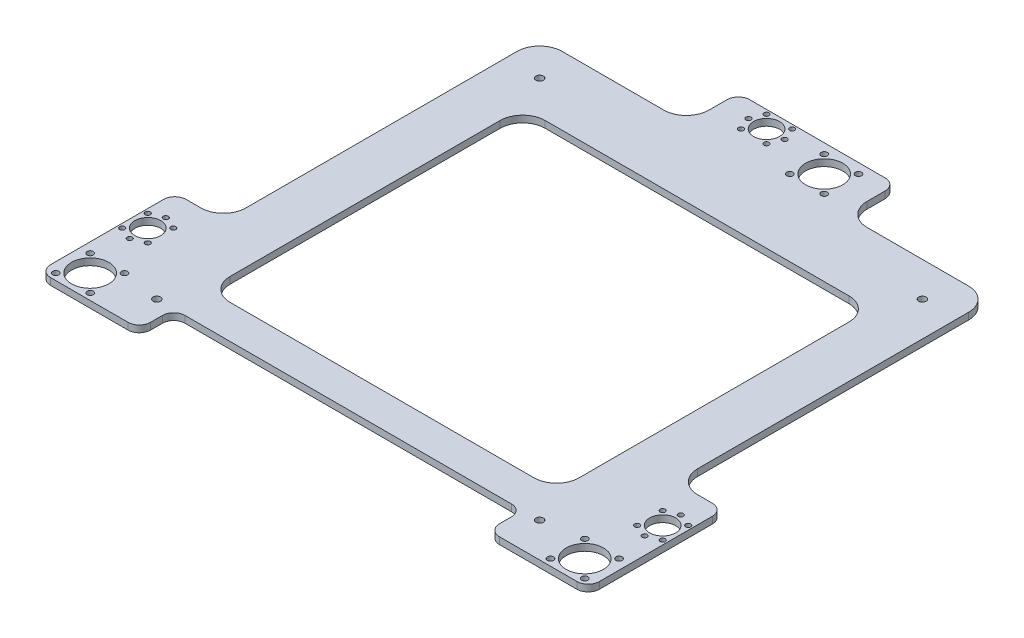
SolidWorks part; units mm, degrees
material "Plain Carbon Steel"
ref_plane "Front Plane" through (0, 0, 0) normal (0, 0, 1) x (1, 0, 0)
ref_plane "Top Plane" through (0, 0, 0) normal (0, 1, 0) x (1, 0, 0)
ref_plane "Right Plane" through (0, 0, 0) normal (1, 0, 0) x (0, 0, -1)
sketch "Sketch1" plane through (0, 0, 0) normal (0, 1, 0) x (1, 0, 0)
  line L0 (-243, -200) -> (243, -200)
  line L1 (-169.5, 169.5) -> (169.5, 169.5)
  line L2 (-169.5, 169.5) -> (-169.5, -169.5)
  line L3 (-169.5, -169.5) -> (169.5, -169.5)
  line L4 (169.5, 169.5) -> (169.5, -169.5)
  line L5 (-169.5, 169.5) -> (169.5, -169.5) construction
  line L6 (-169.5, -169.5) -> (169.5, 169.5) construction
  line L7 (-243, -200) -> (-243, 246)
  line L8 (-243, 246) -> (243, 246)
  line L9 (243, 246) -> (243, -200)
  line L10 (0, 0) -> (0, -200)
  point P0 (0, 0)
  dimension "D1" = 339
  dimension "D2" = 446
  dimension "D3" = 486
  dimension "D4" = 200
sketch "Sketch2" plane through (0, 0, 0) normal (0, 1, 0) x (1, 0, 0)
  line L0 (243, 246) -> (243, -200) construction
  line L1 (-243, 246) -> (243, 246) construction
  line L2 (-243, -200) -> (-243, 246) construction
  line L3 (-243, -200) -> (243, -200) construction
  line L4 (243, 246) -> (243, -200)
  line L5 (-243, 246) -> (243, 246)
  line L6 (-243, -200) -> (-243, 246)
  line L7 (-243, -200) -> (243, -200)
extrude "Boss-Extrude1" add sketch "Sketch2" along normal blind 6
sketch "Sketch3" plane through (0, 6, 0) normal (0, 1, 0) x (1, 0, 0)
  circle A0 centre (-203.7972, -194.2028) radius 2.75 construction
  circle A1 centre (-234.2028, -194.2028) radius 2.75 construction
  circle A2 centre (-234.2028, -163.7972) radius 2.75 construction
  circle A3 centre (-203.7972, -163.7972) radius 2.75 construction
  circle A4 centre (-203.7972, -194.2028) radius 2.75
  circle A5 centre (-234.2028, -194.2028) radius 2.75
  circle A6 centre (-234.2028, -163.7972) radius 2.75
  circle A7 centre (-203.7972, -163.7972) radius 2.75
  circle A8 centre (-239.3137, -107.6863) radius 2.35 construction
  circle A9 centre (-239.3137, -107.6863) radius 2.35 construction
  circle A10 centre (-239.3137, -130.3137) radius 2.35 construction
  circle A11 centre (-239.3137, -130.3137) radius 2.35 construction
  circle A12 centre (-228, -135) radius 2.35 construction
  circle A13 centre (-228, -135) radius 2.35 construction
  circle A14 centre (-216.6863, -130.3137) radius 2.35 construction
  circle A15 centre (-216.6863, -130.3137) radius 2.35 construction
  circle A16 centre (-216.6863, -107.6863) radius 2.35 construction
  circle A17 centre (-216.6863, -107.6863) radius 2.35 construction
  circle A18 centre (-228, -103) radius 2.35 construction
  circle A19 centre (-228, -103) radius 2.35 construction
  circle A20 centre (-239.3137, -107.6863) radius 2.35
  circle A21 centre (-239.3137, -107.6863) radius 2.35
  circle A22 centre (-239.3137, -130.3137) radius 2.35
  circle A23 centre (-239.3137, -130.3137) radius 2.35
  circle A24 centre (-228, -135) radius 2.35
  circle A25 centre (-228, -135) radius 2.35
  circle A26 centre (-216.6863, -130.3137) radius 2.35
  circle A27 centre (-216.6863, -130.3137) radius 2.35
  circle A28 centre (-216.6863, -107.6863) radius 2.35
  circle A29 centre (-216.6863, -107.6863) radius 2.35
  circle A30 centre (-228, -103) radius 2.35
  circle A31 centre (-228, -103) radius 2.35
  circle A32 centre (-228, -119) radius 11 construction
  circle A33 centre (-219, -179) radius 16 construction
  circle A34 centre (-228, -119) radius 11
  circle A35 centre (-219, -179) radius 16
  circle A36 centre (-18.6863, 242.3137) radius 2.35 construction
  circle A37 centre (-18.6863, 242.3137) radius 2.35 construction
  circle A38 centre (-41.3137, 242.3137) radius 2.35 construction
  circle A39 centre (-41.3137, 242.3137) radius 2.35 construction
  circle A40 centre (-46, 231) radius 2.35 construction
  circle A41 centre (-46, 231) radius 2.35 construction
  circle A42 centre (-41.3137, 219.6863) radius 2.35 construction
  circle A43 centre (-41.3137, 219.6863) radius 2.35 construction
  circle A44 centre (-18.6863, 219.6863) radius 2.35 construction
  circle A45 centre (-18.6863, 219.6863) radius 2.35 construction
  circle A46 centre (-14, 231) radius 2.35 construction
  circle A47 centre (-14, 231) radius 2.35 construction
  circle A48 centre (-18.6863, 242.3137) radius 2.35
  circle A49 centre (-18.6863, 242.3137) radius 2.35
  circle A50 centre (-41.3137, 242.3137) radius 2.35
  circle A51 centre (-41.3137, 242.3137) radius 2.35
  circle A52 centre (-46, 231) radius 2.35
  circle A53 centre (-46, 231) radius 2.35
  circle A54 centre (-41.3137, 219.6863) radius 2.35
  circle A55 centre (-41.3137, 219.6863) radius 2.35
  circle A56 centre (-18.6863, 219.6863) radius 2.35
  circle A57 centre (-18.6863, 219.6863) radius 2.35
  circle A58 centre (-14, 231) radius 2.35
  circle A59 centre (-14, 231) radius 2.35
  circle A60 centre (-30, 231) radius 11 construction
  circle A61 centre (30, 222) radius 16 construction
  circle A62 centre (45.2028, 237.2028) radius 2.75 construction
  circle A63 centre (14.7972, 237.2028) radius 2.75 construction
  circle A64 centre (14.7972, 206.7972) radius 2.75 construction
  circle A65 centre (45.2028, 206.7972) radius 2.75 construction
  circle A66 centre (-30, 231) radius 11
  circle A67 centre (30, 222) radius 16
  circle A68 centre (45.2028, 237.2028) radius 2.75
  circle A69 centre (14.7972, 237.2028) radius 2.75
  circle A70 centre (14.7972, 206.7972) radius 2.75
  circle A71 centre (45.2028, 206.7972) radius 2.75
hole_wizard "M5 Clearance Hole1" positions "Sketch4" profile "Sketch5" hole size "M5" standard "ANSI Metric" end condition through all
sketch "Sketch4" plane through (0, 6, 0) normal (0, 1, 0) x (1, 0, 0)
  point P0 (-234.2028, -163.7972)
  point P3 (-203.7972, -163.7972)
  point P6 (-203.7972, -194.2028)
  point P9 (-234.2028, -194.2028)
sketch "Sketch5" plane through (-234.2028, 6, 163.7972) normal (1, 0, 0) x (0, 0, 1)
  line L0 (0, 0) -> (0, 6)
  line L1 (0, 6) -> (2.75, 6)
  line L2 (2.75, 6) -> (2.75, 0)
  line L5 (2.75, 0) -> (0, 0)
  line L11 (0, -6.35) -> (0, 107.95) construction
  dimension "Thru Hole Dia." = 5.5
  dimension "Thru Hole Depth" = 6
hole_wizard "M4 Clearance Hole1" positions "Sketch6" profile "Sketch7" hole size "M4" standard "ANSI Metric" end condition through all
sketch "Sketch6" plane through (0, 6, 0) normal (0, 1, 0) x (1, 0, 0)
  point P0 (-228, -135)
  point P3 (-216.6863, -130.3137)
  point P6 (-216.6863, -107.6863)
  point P9 (-228, -103)
  point P12 (-239.3137, -107.6863)
  point P15 (-239.3137, -130.3137)
sketch "Sketch7" plane through (-228, 6, 135) normal (1, 0, 0) x (0, 0, 1)
  line L0 (0, 0) -> (0, 6)
  line L1 (0, 6) -> (2.25, 6)
  line L2 (2.25, 6) -> (2.25, 0)
  line L5 (2.25, 0) -> (0, 0)
  line L11 (0, -6.35) -> (0, 107.95) construction
  dimension "Thru Hole Dia." = 4.5
  dimension "Thru Hole Depth" = 6
sketch "Sketch8" plane through (0, 6, 0) normal (0, 1, 0) x (1, 0, 0)
  circle A0 centre (-228, -119) radius 11.5
  circle A1 centre (-219, -179) radius 16.5
  circle A2 centre (-219, -179) radius 16 construction
  circle A3 centre (-228, -119) radius 11 construction
  dimension "D1" = 0.5
  dimension "D2" = 0.5
extrude "Cut-Extrude1" cut sketch "Sketch8" against normal through all
mirror "Mirror1" about plane through (0, 0, 0) normal (1, 0, 0) of "Cut-Extrude1", "M4 Clearance Hole1", "M5 Clearance Hole1"
hole_wizard "M5 Clearance Hole2" positions "Sketch9" profile "Sketch10" hole size "M5" standard "ANSI Metric" end condition through all
sketch "Sketch9" plane through (0, 6, 0) normal (0, 1, 0) x (1, 0, 0)
  point P0 (45.2028, 206.7972)
  point P3 (14.7972, 206.7972)
  point P6 (14.7972, 237.2028)
  point P9 (45.2028, 237.2028)
sketch "Sketch10" plane through (45.2028, 6, -206.7972) normal (1, 0, 0) x (0, 0, 1)
  line L0 (0, 0) -> (0, 6)
  line L1 (0, 6) -> (2.75, 6)
  line L2 (2.75, 6) -> (2.75, 0)
  line L5 (2.75, 0) -> (0, 0)
  line L11 (0, -6.35) -> (0, 107.95) construction
  dimension "Thru Hole Dia." = 5.5
  dimension "Thru Hole Depth" = 6
hole_wizard "M4 Clearance Hole2" positions "Sketch11" profile "Sketch12" hole size "M4" standard "ANSI Metric" end condition through all
sketch "Sketch11" plane through (0, 6, 0) normal (0, 1, 0) x (1, 0, 0)
  point P0 (-41.3137, 219.6863)
  point P3 (-46, 231)
  point P6 (-41.3137, 242.3137)
  point P9 (-18.6863, 242.3137)
  point P12 (-14, 231)
  point P15 (-18.6863, 219.6863)
sketch "Sketch12" plane through (-41.3137, 6, -219.6863) normal (1, 0, 0) x (0, 0, 1)
  line L0 (0, 0) -> (0, 6)
  line L1 (0, 6) -> (2.25, 6)
  line L2 (2.25, 6) -> (2.25, 0)
  line L5 (2.25, 0) -> (0, 0)
  line L11 (0, -6.35) -> (0, 107.95) construction
  dimension "Thru Hole Dia." = 4.5
  dimension "Thru Hole Depth" = 6
sketch "Sketch13" plane through (0, 6, 0) normal (0, 1, 0) x (1, 0, 0)
  circle A0 centre (-30, 231) radius 11.5
  circle A1 centre (30, 222) radius 16.5
  circle A3 centre (-228, -119) radius 11.5 construction
  circle A4 centre (-219, -179) radius 16.5 construction
extrude "Cut-Extrude2" cut sketch "Sketch13" against normal through all
hole_wizard "M6 Clearance Hole1" positions "Sketch15" profile "Sketch16" hole size "M6" standard "ANSI Metric" end condition through all
sketch "Sketch15" plane through (0, 6, 0) normal (0, 1, 0) x (1, 0, 0)
  point P0 (-169.5, -169.5)
  point P2 (-169.5, 169.5)
  point P4 (169.5, 169.5)
  point P6 (169.5, -169.5)
sketch "Sketch16" plane through (-169.5, 6, 169.5) normal (1, 0, 0) x (0, 0, 1)
  line L0 (0, 0) -> (0, 6)
  line L1 (0, 6) -> (3.3, 6)
  line L2 (3.3, 6) -> (3.3, 0)
  line L5 (3.3, 0) -> (0, 0)
  line L11 (0, -6.35) -> (0, 107.95) construction
  dimension "Thru Hole Dia." = 6.6
  dimension "Thru Hole Depth" = 6
sketch "Sketch17" plane through (0, 6, 0) normal (0, 1, 0) x (1, 0, 0)
  line L1 (154.5, 139.5) -> (-154.5, 139.5)
  line L2 (154.5, 139.5) -> (154.5, -139.5)
  line L3 (154.5, -139.5) -> (-154.5, -139.5)
  line L4 (-154.5, 139.5) -> (-154.5, -139.5)
  line L5 (154.5, 139.5) -> (-154.5, -139.5) construction
  line L6 (154.5, -139.5) -> (-154.5, 139.5) construction
  point P0 (0, 0)
  dimension "D1" = 15
  dimension "D2" = 30
extrude "Cut-Extrude3" cut sketch "Sketch17" against normal through all
sketch "Sketch18" plane through (0, 6, 0) normal (0, 1, 0) x (1, 0, 0)
  line L0 (-243, -200) -> (243, -200) construction
  line L1 (-154.5, -200) -> (154.5, -200)
  line L2 (-154.5, -200) -> (-154.5, -169.5)
  line L3 (-154.5, -169.5) -> (154.5, -169.5)
  line L4 (154.5, -200) -> (154.5, -169.5)
  line L5 (-169.5, -169.5) -> (169.5, -169.5) construction
  line L6 (0, -169.5) -> (0, 0) construction
  dimension "D1" = 15
extrude "Cut-Extrude4" cut sketch "Sketch18" against normal through all
sketch "Sketch19" plane through (0, 6, 0) normal (0, 1, 0) x (1, 0, 0)
  line L0 (-243, -80) -> (-200, -80)
  line L1 (-243, 246) -> (-243, -200) construction
  line L2 (-200, -80) -> (-200, 200)
  line L3 (-200, 200) -> (-70, 200)
  line L4 (-70, 200) -> (-70, 246)
  line L5 (243, 246) -> (-243, 246) construction
  line L6 (0, 0) -> (0, -200) construction
  line L7 (-243, -200) -> (243, -200) construction
  line L8 (-243, -80) -> (-243, 246)
  line L9 (-243, 246) -> (-70, 246)
  dimension "D1" = 200
  dimension "D2" = 200
  dimension "D3" = 70
  dimension "D4" = 120
extrude "Cut-Extrude5" cut sketch "Sketch19" against normal through all
mirror "Mirror2" about plane through (0, 0, 0) normal (1, 0, 0) of "Cut-Extrude5"
fillet "Fillet1" radius 10 10 edges at (-70, 3, -246) (70, 3, -246) (243, 3, 80) (243, 3, 200) (-243, 3, 80) (-243, 3, 200) (-154.5, 3, 200) (-154.5, 3, 169.5) (154.5, 3, 200) (154.5, 3, 169.5)
fillet "Fillet2" radius 20 10 edges at (200, 3, -200) (-200, 3, -200) (-154.5, 3, 139.5) (154.5, 3, 139.5) (154.5, 3, -139.5) (-154.5, 3, -139.5) (-200, 3, 80) (-70, 3, -200) (70, 3, -200) (200, 3, 80)
